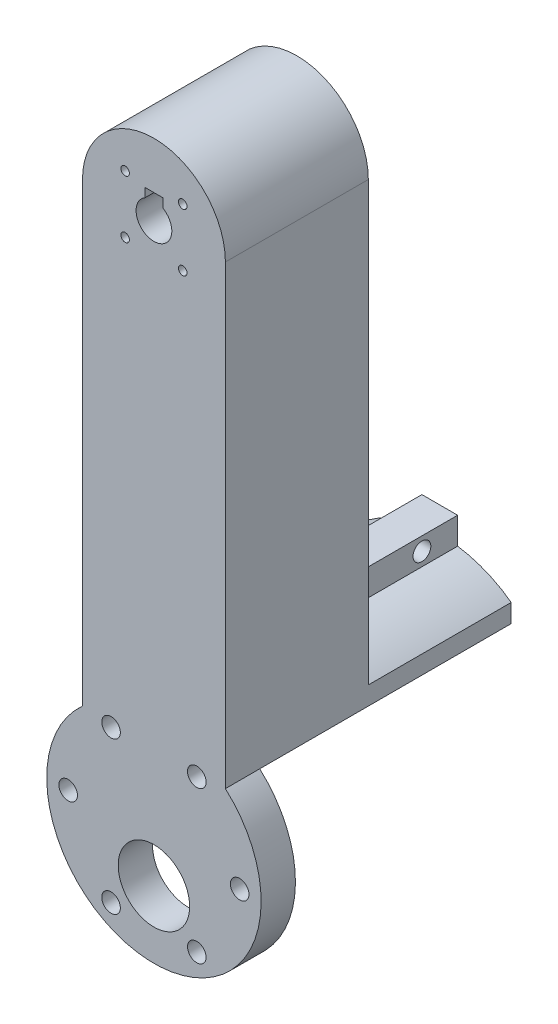
SolidWorks part; units mm, degrees
ref_plane "Front Plane" through (0, 0, 0) normal (0, 0, 1) x (1, 0, 0)
ref_plane "Top Plane" through (0, 0, 0) normal (0, 1, 0) x (1, 0, 0)
ref_plane "Right Plane" through (0, 0, 0) normal (1, 0, 0) x (0, 0, -1)
sketch "Sketch1" plane through (0, 0, 0) normal (0, 0, 1) x (1, 0, 0)
  line L0 (-5.1187, 55.9187) -> (5.1187, 45.6813) construction
  line L2 (12.7, 50.8) -> (12.7, -50.8)
  line L4 (-12.7, 50.8) -> (-12.7, -50.8)
  line L5 (12.7, 50.8) -> (-12.7, -50.8) construction
  line L6 (12.7, -50.8) -> (-12.7, 50.8) construction
  line L7 (5.1187, 55.9187) -> (-5.1187, 45.6813) construction
  line L8 (0, 50.8) -> (0, 51.7208) construction
  arc A0 (-12.7, 50.8) -> (12.7, 50.8) centre (0, 50.8) cw
  arc A1 (12.7, -50.8) -> (-12.7, -50.8) centre (0, -50.8) cw
  circle A2 centre (0, 50.8) radius 3.175
  circle A3 centre (-5.1187, 55.9187) radius 0.762
  circle A4 centre (5.1187, 55.9187) radius 0.762
  circle A5 centre (5.1187, 45.6813) radius 0.762
  circle A6 centre (-5.1187, 45.6813) radius 0.762
  point P0 (0, 0)
  point P14 (0, 50.8)
  point P15 (0, 50.8)
  dimension "D3" = 6.35
  dimension "D6" = 1.524
  dimension "D1" = 25.4
  dimension "D2" = 101.6
  dimension "D4" = 45
  dimension "D5" = 14.478
extrude "Boss-Extrude1" add sketch "Sketch1" along normal blind 25.4
sketch "Sketch2" plane through (0, 0, 0) normal (0, 0, -1) x (-1, 0, 0)
  circle A0 centre (0, -44.45) radius 19.05
  arc A2 (-12.7, -50.8) -> (12.7, -50.8) centre (0, -50.8) ccw construction
  dimension "D1" = 38.1
extrude "Boss-Extrude2" add sketch "Sketch2" against normal blind 25.4
sketch "Sketch4" plane through (0, 0, 25.4) normal (0, 0, 1) x (1, 0, 0)
  circle A0 centre (0, -44.45) radius 19.05
  arc A1 (-12.7, -30.251) -> (12.7, -30.251) centre (0, -44.45) ccw construction
  dimension "D1" = 38.1
sketch "Sketch3" plane through (0, 0, 25.4) normal (0, 0, 1) x (1, 0, 0)
  line L0 (-15.24, -44.45) -> (15.24, -44.45) construction
  line L1 (15.24, -44.45) -> (7.62, -30.9593) construction
  line L2 (-15.24, -44.45) -> (-7.62, -30.9593) construction
  line L3 (-15.24, -44.45) -> (-7.62, -57.9407) construction
  line L4 (15.24, -44.45) -> (7.62, -57.9407) construction
  circle A0 centre (-7.62, -30.9593) radius 1.651
  circle A1 centre (7.62, -30.9593) radius 1.651
  circle A2 centre (-15.24, -44.45) radius 1.651
  circle A3 centre (-7.62, -57.9407) radius 1.651
  circle A4 centre (7.62, -57.9407) radius 1.651
  circle A5 centre (15.24, -44.45) radius 1.651
  point P10 (0, -44.45)
  dimension "D5" = 3.302
  dimension "D1" = 30.48
  dimension "D2" = 15.494
  dimension "D3" = 30.988
  dimension "D4" = 15.24
extrude "Cut-Extrude1" cut sketch "Sketch3" against normal blind 25.4
sketch "Sketch5" plane through (0, 0, 25.4) normal (0, 0, 1) x (1, 0, 0)
  circle A0 centre (0, -51.562) radius 6.35
  dimension "D1" = 12.7
  dimension "D2" = 7.112
extrude "Cut-Extrude2" cut sketch "Sketch5" against normal blind 25.4
sketch "Sketch6" plane through (0, 0, 0) normal (0, 0, -1) x (-1, 0, 0)
  line L1 (-1.5875, 55.1371) -> (1.5875, 55.1371)
  line L2 (-1.5875, 55.1371) -> (-1.5875, 53.5496)
  line L3 (-1.5875, 53.5496) -> (1.5875, 53.5496)
  line L4 (1.5875, 55.1371) -> (1.5875, 53.5496)
  circle A0 centre (0, 50.8) radius 3.175 construction
  dimension "D1" = 3.175
  dimension "D2" = 1.5875
extrude "Cut-Extrude3" cut sketch "Sketch6" against normal blind 25.4
sketch "Sketch8" plane through (0, 0, 0) normal (0, 0, -1) x (-1, 0, 0)
  circle A0 centre (0, -44.45) radius 19.05
  dimension "D1" = 38.1
extrude "Cut-Extrude4" cut sketch "Sketch8" against normal blind 19.3
sketch "Sketch9" plane through (0, 0, 0) normal (0, 0, -1) x (-1, 0, 0)
  line L0 (12.7, 50.8) -> (12.7, -30.251) construction
  line L1 (-12.7, -30.251) -> (-12.7, 50.8) construction
  line L2 (-12.7, -30.251) -> (-12.7, -26.9904)
  line L3 (12.7, -30.251) -> (12.7, -26.9904)
  arc A0 (-12.7, -30.251) -> (12.7, -30.251) centre (0, -44.45) cw
  arc A1 (-12.7, -26.9904) -> (12.7, -26.9904) centre (0, -44.45) cw
  dimension "D1" = 2.54
extrude "Boss-Extrude3" add sketch "Sketch9" along normal blind 25.4
sketch "Sketch10" plane through (0, 0, 0) normal (0, 0, -1) x (-1, 0, 0)
  line L1 (-3.175, -18.3322) -> (3.175, -18.3322)
  line L2 (-3.175, -18.3322) -> (-3.175, -23.0947)
  line L3 (-3.175, -23.0947) -> (3.175, -23.0947)
  line L4 (3.175, -18.3322) -> (3.175, -23.0947)
  arc A0 (12.7, -26.9904) -> (-12.7, -26.9904) centre (0, -44.45) ccw construction
  point P4 (0, -18.3322)
  dimension "D1" = 6.35
  dimension "D2" = 4.7625
extrude "Boss-Extrude4" add sketch "Sketch10" along normal up to surface (25.4 mm away) up to face at (0, -26.3753, -25.4)
sketch "Sketch11" plane through (3.175, 0, 0) normal (1, 0, 0) x (0, 0, -1)
  line L0 (24.0343, -18.3322) -> (24.0343, -23.0947) construction
  line L1 (25.4, -18.3322) -> (0, -18.3322) construction
  line L2 (25.4, -23.0947) -> (0, -23.0947) construction
  line L3 (0, -26.9904) -> (0, 50.8) construction
  line L4 (25.4, -23.0947) -> (25.4, -18.3322) construction
  circle A0 centre (6.35, -20.7135) radius 1.5875
  circle A1 centre (19.05, -20.7135) radius 1.5875
  point P9 (24.0343, -20.7135)
  dimension "D1" = 3.175
  dimension "D2" = 6.35
  dimension "D3" = 6.35
extrude "Cut-Extrude5" cut sketch "Sketch11" against normal through all
ref_plane "Plane1" through (0, 0, 12.7) normal (0, 0, 1) x (1, 0, 0)
ref_axis "Axis1" through (0, 50.8, 25.4) along (0, 0, -1)
ref_point "Point1"
ref_plane "Plane2" through (0, 0, 37.2197) normal (0, 0, -1) x (-1, 0, 0)
ref_axis "Axis2" through (-0.0899, -51.3847, 78.2641) along (0, 0, -1)
ref_point "wheel orgin point"
